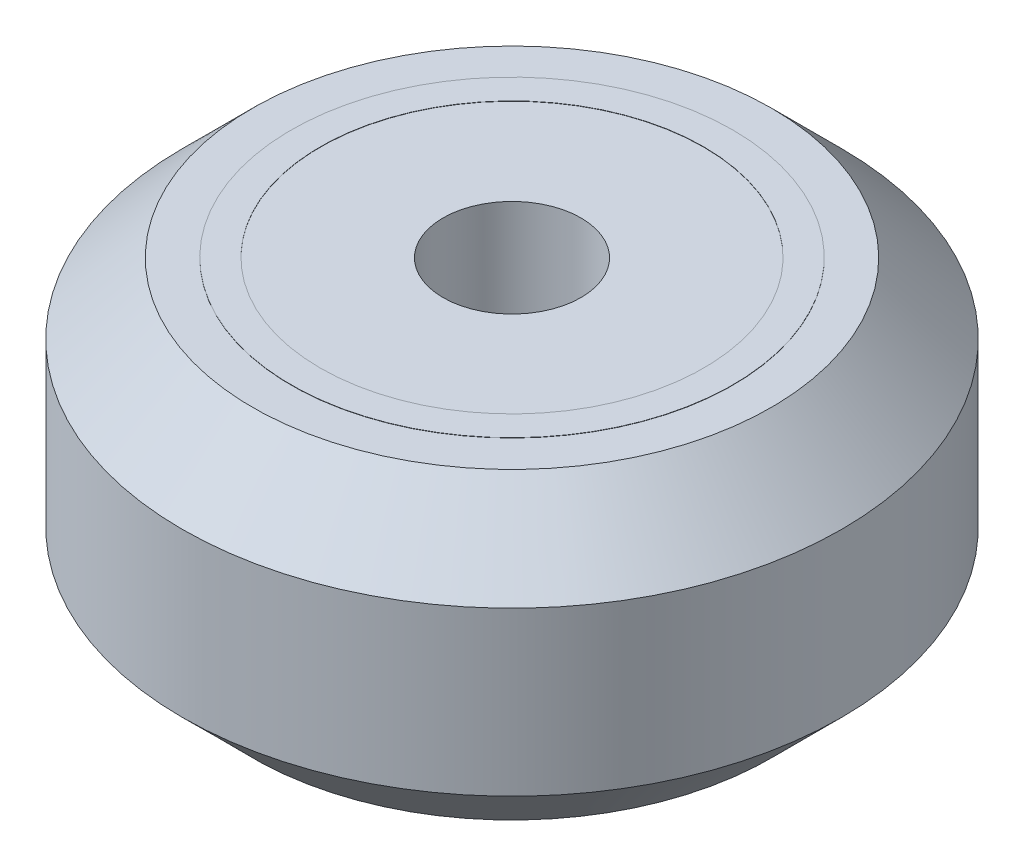
SolidWorks part; units mm, degrees
ref_plane "Front Plane" through (0, 0, 0) normal (0, 0, 1) x (1, 0, 0)
ref_plane "Top Plane" through (0, 0, 0) normal (0, 1, 0) x (1, 0, 0)
ref_plane "Right Plane" through (0, 0, 0) normal (1, 0, 0) x (0, 0, -1)
sketch "Sketch1" plane through (0, 0, 0) normal (0, 0, 1) x (1, 0, 0)
  line L0 (0, 5.5) -> (9.395, 5.5)
  line L1 (0, -55) -> (0, 55) construction
  line L2 (9.395, 5.5) -> (11.945, 2.95)
  line L3 (11.945, 2.95) -> (11.945, -2.95)
  line L4 (11.945, -2.95) -> (9.395, -5.5)
  line L5 (9.395, -5.5) -> (0, -5.5)
  line L6 (0, -5.5) -> (0, 5.5)
  line L7 (0, 0) -> (0, 44.8382) construction
  point P11 (0, 0)
  dimension "D1" = 11
  dimension "D2" = 5.9
  dimension "D3" = 45
  dimension "D4" = 11.945
revolve "Revolve1" add sketch "Sketch1" angle 360 about L7
sketch "Sketch2" plane through (0, -5.5, 0) normal (0, -1, 0) x (-1, 0, 0)
  circle A0 centre (0, 0) radius 2.5
  dimension "D1" = 5
extrude "Cut-Extrude1" cut sketch "Sketch2" against normal up to next
sketch "Sketch3" plane through (0, -5.5, 0) normal (0, -1, 0) x (1, 0, 0)
  circle A0 centre (0, 0) radius 6.945
  circle A1 centre (0, 0) radius 8
  circle M1 centre (0, 0) radius 2.5
  dimension "D1" = 16
  dimension "D2" = 13.89
sketch "Sketch4" plane through (0, 5.5, 0) normal (0, 1, 0) x (1, 0, 0)
  circle A0 centre (0, 0) radius 6.945
  circle A1 centre (0, 0) radius 8
  dimension "D1" = 16
  dimension "D2" = 13.89
extrude "Boss-Extrude1" add sketch "Sketch4" along normal blind 0.01 contours A1 A0 region at (-7.7737, 5.5, 0)
extrude "Boss-Extrude2" add sketch "Sketch3" along normal blind 0.01 contours M1 | A0 | A1 region at (0, -5.5, 0)
